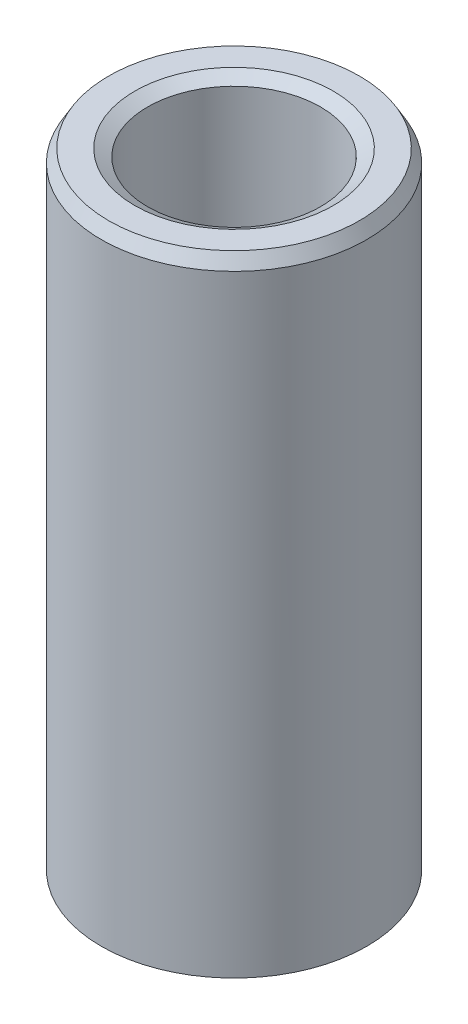
SolidWorks part; units mm, degrees
ref_plane "Front Plane" through (0, 0, 0) normal (0, 0, 1) x (1, 0, 0)
ref_plane "Top Plane" through (0, 0, 0) normal (0, 1, 0) x (1, 0, 0)
ref_plane "Right Plane" through (0, 0, 0) normal (1, 0, 0) x (0, 0, -1)
sketch "Sketch1" plane through (0, 0, 0) normal (0, 1, 0) x (1, 0, 0)
  circle A0 centre (0, 0) radius 15
  dimension "SLEEVE_OD" = 30
extrude "Boss-Extrude1" add sketch "Sketch1" along normal blind 71.4395
sketch "Sketch2" plane through (0, 0, 0) normal (0, 1, 0) x (1, 0, 0)
  circle A0 centre (0, 0) radius 9.7755
  dimension "BORE_D" = 19.5511
extrude "Cut-Extrude1" cut sketch "Sketch2" along normal through all
chamfer "Chamfer1" distance 1.4395 angle 30 4 edges at (0, 71.4395, 9.7755) (0, 0, 9.7755) (0, 0, 15) (0, 71.4395, 15) first distance on face at (0, 71.4395, 9.7755) first distance on face at (0, 0, 9.7755) first distance on face at (0, 71.4395, 15)
